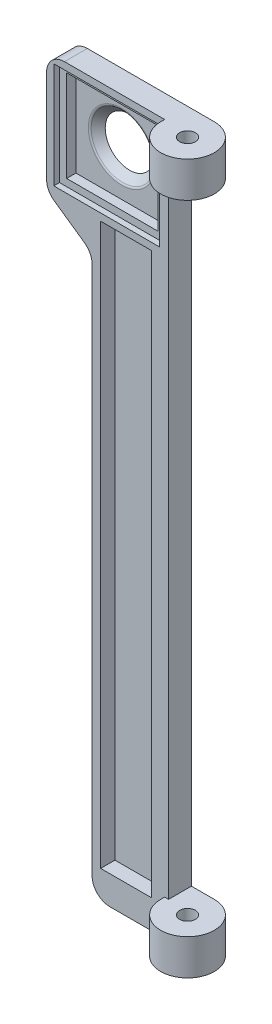
SolidWorks part; units mm, degrees
ref_plane "Front Plane" through (0, 0, 0) normal (0, 0, 1) x (1, 0, 0)
ref_plane "Top Plane" through (0, 0, 0) normal (0, 1, 0) x (1, 0, 0)
ref_plane "Right Plane" through (0, 0, 0) normal (1, 0, 0) x (0, 0, -1)
sketch "Sketch1" plane through (0, 0, 0) normal (0, 0, 1) x (1, 0, 0)
  line L1 (0, 0) -> (15.875, 0)
  line L2 (0, 0) -> (0, 125.984)
  line L3 (0, 125.984) -> (15.875, 125.984)
  line L4 (15.875, 0) -> (15.875, 125.984)
  line L5 (10.541, 5.08) -> (8.636, 5.08)
  line L6 (10.541, 5.08) -> (10.541, 120.904)
  line L7 (10.541, 120.904) -> (8.636, 120.904)
  line L8 (8.636, 5.08) -> (8.636, 120.904)
  point P9 (7.9375, 125.984)
  point P10 (9.5885, 5.08)
  dimension "D1" = 125.984
  dimension "D2" = 15.875
  dimension "D3" = 5.08
  dimension "D4" = 5.08
  dimension "D5" = 1.905
  dimension "D6" = 5.334
extrude "Boss-Extrude1" add sketch "Sketch1" along normal blind 4.064
sketch "Sketch2" plane through (0, 0, 4.064) normal (0, 0, 1) x (1, 0, 0)
  line L1 (8.636, 120.904) -> (1.524, 120.904)
  line L2 (8.636, 120.904) -> (8.636, 5.08)
  line L3 (8.636, 5.08) -> (1.524, 5.08)
  line L4 (1.524, 120.904) -> (1.524, 5.08)
  line L5 (8.636, 5.08) -> (10.541, 5.08) construction
  point P4 (8.382, 5.08)
  dimension "D1" = 7.112
extrude "Cut-Extrude1" cut sketch "Sketch2" against normal blind 2.54
fillet "Fillet1" radius 0.508 1 edges at (8.636, 62.992, 1.524)
sketch "Sketch3" plane through (0, 0, 0) normal (0, 0, -1) x (-1, 0, 0)
  line L1 (-15.875, 125.984) -> (8.0772, 125.984)
  line L2 (-15.875, 125.984) -> (-15.875, 104.648)
  line L3 (-15.875, 104.648) -> (8.0772, 104.648)
  line L4 (8.0772, 125.984) -> (8.0772, 104.648)
  dimension "D1" = 23.9522
  dimension "D2" = 21.336
extrude "Boss-Extrude2" add sketch "Sketch3" against normal up to surface (4.064 mm away) up to face at (7.9375, 62.992, 4.064)
sketch "Sketch4" plane through (0, 0, 4.064) normal (0, 0, 1) x (1, 0, 0)
  line L0 (-8.0772, 115.316) -> (2.5908, 115.316) construction
  line L1 (-5.5372, 123.444) -> (10.7188, 123.444)
  line L2 (-5.5372, 123.444) -> (-5.5372, 107.188)
  line L3 (-5.5372, 107.188) -> (10.7188, 107.188)
  line L4 (10.7188, 123.444) -> (10.7188, 107.188)
  line L5 (-5.5372, 123.444) -> (10.7188, 107.188) construction
  line L6 (-5.5372, 107.188) -> (10.7188, 123.444) construction
  line L9 (-8.0772, 125.984) -> (-8.0772, 104.648) construction
  point P0 (2.5908, 115.316)
  dimension "D1" = 16.256
  dimension "D2" = 2.54
extrude "Cut-Extrude2" cut sketch "Sketch4" against normal blind 2.667 contours L1 L4 L3 L2
sketch "Sketch5" plane through (0, 0, 4.064) normal (0, 0, 1) x (1, 0, 0)
  line L0 (-8.0772, 104.648) -> (0, 104.648) construction
  line L1 (-6.8072, 124.714) -> (11.9888, 124.714)
  line L2 (-6.8072, 124.714) -> (-6.8072, 105.918)
  line L3 (-6.8072, 105.918) -> (11.9888, 105.918)
  line L4 (11.9888, 124.714) -> (11.9888, 105.918)
  line L5 (-6.8072, 124.714) -> (11.9888, 105.918) construction
  line L6 (-6.8072, 105.918) -> (11.9888, 124.714) construction
  line L7 (-8.0772, 125.984) -> (-8.0772, 104.648) construction
  line L9 (15.875, 125.984) -> (-8.0772, 125.984) construction
  point P0 (2.5908, 115.316)
  dimension "D1" = 1.27
  dimension "D2" = 1.27
  dimension "D3" = 1.27
extrude "Cut-Extrude3" cut sketch "Sketch5" against normal blind 1.016
sketch "Sketch6" plane through (0, 0, 1.397) normal (0, 0, 1) x (1, 0, 0)
  line L0 (-5.5372, 115.316) -> (10.7188, 115.316) construction
  line L1 (-5.5372, 123.444) -> (-5.5372, 107.188) construction
  line L2 (10.7188, 107.188) -> (10.7188, 123.444) construction
  circle A0 centre (2.5908, 115.316) radius 5.715
  dimension "D1" = 11.43
extrude "Cut-Extrude4" cut sketch "Sketch6" against normal blind 2.54 draft 45
chamfer "Chamfer1" distance 8.128 angle 35 1 edges at (0, 104.648, 2.032) first distance on face at (-4.0386, 104.648, 2.032)
fillet "Fillet3" radius 3.175 4 edges at (-8.0772, 104.6124, 2.032) (0, 98.9567, 2.032) (0, 0, 2.032) (-8.0772, 125.984, 2.032)
fillet "Fillet4" radius 0.508 1 edges at (8.3058, 115.316, 1.397)
sketch "Sketch7" plane through (0, 0, 0) normal (0, 0, -1) x (-1, 0, 0)
  line L0 (-15.875, 0) -> (-15.875, 125.984) construction
  line L1 (-15.875, 119.634) -> (-13.589, 119.634)
  line L2 (-15.875, 119.634) -> (-15.875, 6.35)
  line L3 (-15.875, 6.35) -> (-13.589, 6.35)
  line L4 (-13.589, 119.634) -> (-13.589, 6.35)
  line L5 (-10.541, 5.08) -> (-10.541, 104.648) construction
  line L6 (-3.175, 0) -> (-15.875, 0) construction
  line L7 (-15.875, 125.984) -> (4.9022, 125.984) construction
  dimension "D1" = 3.048
  dimension "D2" = 6.35
  dimension "D3" = 6.35
extrude "Cut-Extrude5" cut sketch "Sketch7" against normal through all
sketch "Sketch8" plane through (0, 125.984, 0) normal (0, 1, 0) x (1, 0, 0)
  line L0 (15.875, 0) -> (17.653, 0)
  line L1 (12.8905, -4.7625) -> (12.8905, -4.064)
  line L2 (15.875, -4.064) -> (-4.9022, -4.064) construction
  line L3 (12.8905, -4.064) -> (15.875, -4.064)
  line L4 (15.875, -4.064) -> (15.875, 0)
  arc A1 (17.653, 0) -> (12.8905, -4.7625) centre (17.653, -4.7625) cw
  dimension "D2" = 4.7625
  dimension "D1" = 1.778
extrude "Boss-Extrude3" add sketch "Sketch8" against normal up to surface (6.35 mm away) up to face at (14.732, 119.634, 2.032)
sketch "Sketch9" plane through (0, 6.35, 0) normal (0, 1, 0) x (1, 0, 0)
  line L12 (17.653, 0) -> (13.589, 0)
  line L13 (12.8905, -4.064) -> (12.8905, -4.7625)
  line L15 (13.589, -4.064) -> (12.8905, -4.064)
  line L17 (13.589, 0) -> (13.589, -4.064)
  arc A3 (12.8905, -4.7625) -> (17.653, 0) centre (17.653, -4.7625) ccw
extrude "Boss-Extrude4" add sketch "Sketch9" against normal up to surface (6.35 mm away) up to face at (9.525, 0, 2.032)
sketch "Sketch10" plane through (0, 125.984, 0) normal (0, 1, 0) x (1, 0, 0)
  circle A0 centre (17.653, -4.7625) radius 1.397
  arc A2 (12.8905, -4.7625) -> (17.653, 0) centre (17.653, -4.7625) ccw construction
  dimension "D1" = 2.794
extrude "Cut-Extrude6" cut sketch "Sketch10" against normal through all
